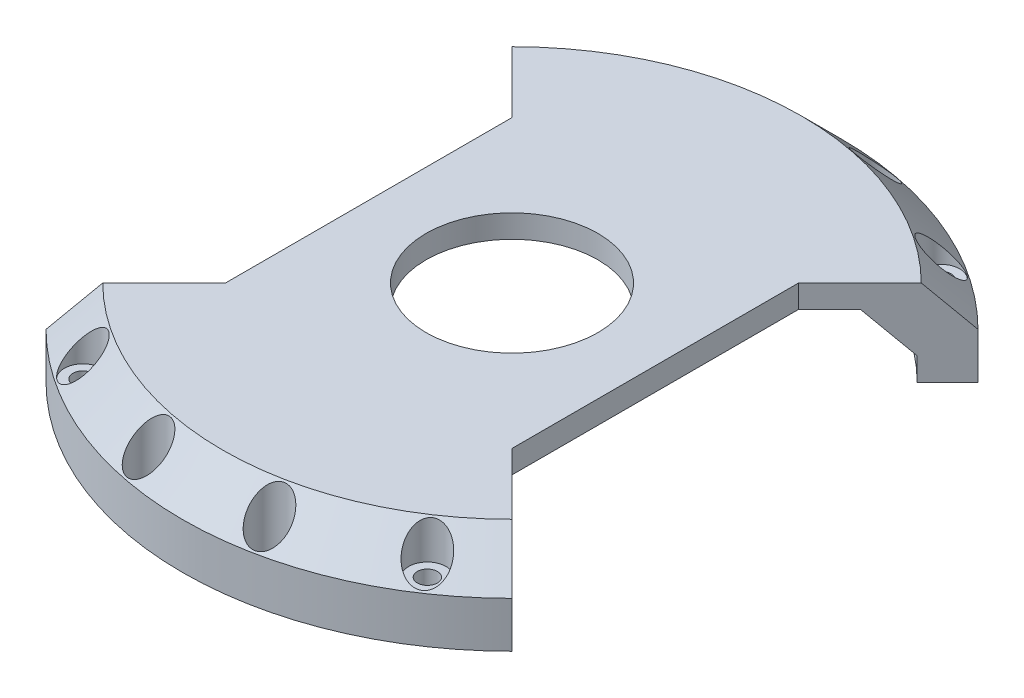
SolidWorks part; units mm, degrees
ref_plane "Front Plane" through (0, 0, 0) normal (0, 0, 1) x (1, 0, 0)
ref_plane "Top Plane" through (0, 0, 0) normal (0, 1, 0) x (1, 0, 0)
ref_plane "Right Plane" through (0, 0, 0) normal (1, 0, 0) x (0, 0, -1)
sketch "Sketch1" plane through (0, 0, 0) normal (0, 1, 0) x (1, 0, 0)
  circle A0 centre (0, 0) radius 57.5
  dimension "D1" = 115
extrude "Boss-Extrude1" add sketch "Sketch1" along normal blind 15
sketch "Sketch2" plane through (0, 0, 0) normal (0, -1, 0) x (1, 0, 0)
  circle A0 centre (0, 0) radius 50
  dimension "D1" = 100
extrude "Cut-Extrude1" cut sketch "Sketch2" against normal blind 11
sketch "Sketch3" plane through (0, 15, 0) normal (0, 1, 0) x (1, 0, 0)
  line L0 (0, 0) -> (0, 54) construction
  line L1 (0, 0) -> (-10.6273, 52.9439) construction
  circle A0 centre (0, 0) radius 54 construction
  circle A13 centre (0, 0) radius 15
  circle A14 centre (-10.6273, 52.9439) radius 1.75
  circle A15 centre (10.4424, 52.9807) radius 1.75
  circle A16 centre (29.9224, 44.9517) radius 1.75
  circle A17 centre (44.8469, 30.0791) radius 1.75
  circle A18 centre (52.9439, 10.6273) radius 1.75
  circle A19 centre (52.9807, -10.4424) radius 1.75
  circle A20 centre (44.9517, -29.9224) radius 1.75
  circle A21 centre (30.0791, -44.8469) radius 1.75
  circle A22 centre (10.6273, -52.9439) radius 1.75
  circle A23 centre (-10.4424, -52.9807) radius 1.75
  circle A24 centre (-29.9224, -44.9517) radius 1.75
  circle A25 centre (-44.8469, -30.0791) radius 1.75
  circle A26 centre (-52.9439, -10.6273) radius 1.75
  circle A27 centre (-52.9807, 10.4424) radius 1.75
  circle A28 centre (-44.9517, 29.9224) radius 1.75
  circle A29 centre (-30.0791, 44.8469) radius 1.75
  point P29 (0, 0)
  point P40 (0, 0)
  dimension "D1" = 108
  dimension "D2" = 11.35
  dimension "D4" = 30
  dimension "D3" = 3.5
extrude "Cut-Extrude2" cut sketch "Sketch3" against normal blind 15
sketch "Sketch4" plane through (0, 15, 0) normal (0, 1, 0) x (1, 0, 0)
  line L0 (25, 25) -> (40.6586, 40.6586)
  line L1 (-25, 25) -> (25, 25) construction
  line L2 (-25, 25) -> (-25, -25) construction
  line L3 (-25, -25) -> (25, -25) construction
  line L4 (25, 25) -> (25, -25)
  line L5 (-25, 25) -> (25, -25) construction
  line L6 (-25, -25) -> (25, 25) construction
  line L7 (25, -25) -> (40.6586, -40.6586)
  circle A0 centre (0, 0) radius 57.5 construction
  arc A1 (40.6586, -40.6586) -> (40.6586, 40.6586) centre (0, 0) ccw
  point P0 (0, 0)
  dimension "D1" = 50
extrude "Cut-Extrude3" cut sketch "Sketch4" against normal blind 15
mirror "Mirror1" about plane through (0, 0, 0) normal (1, 0, 0) of "Cut-Extrude3"
chamfer "Chamfer1" distance 7 angle 45 4 edges at (0, 15, -57.5) (0, 15, 57.5) (0, 11, 50) (0, 11, -50)
sketch "Sketch5" plane through (0, 15, 0) normal (0, 1, 0) x (1, 0, 0)
  line L0 (0, 0) -> (-10.6273, 52.9439) construction
  circle A0 centre (0, 0) radius 54 construction
  circle A1 centre (-10.6273, 52.9439) radius 3.25
  circle A2 centre (10.4424, 52.9807) radius 3.25
  circle A3 centre (29.9224, 44.9517) radius 3.25
  circle A4 centre (44.8469, 30.0791) radius 3.25
  circle A5 centre (52.9439, 10.6273) radius 3.25
  circle A6 centre (52.9807, -10.4424) radius 3.25
  circle A7 centre (44.9517, -29.9224) radius 3.25
  circle A8 centre (30.0791, -44.8469) radius 3.25
  circle A9 centre (10.6273, -52.9439) radius 3.25
  circle A10 centre (-10.4424, -52.9807) radius 3.25
  circle A11 centre (-29.9224, -44.9517) radius 3.25
  circle A12 centre (-44.8469, -30.0791) radius 3.25
  circle A13 centre (-52.9439, -10.6273) radius 3.25
  circle A14 centre (-52.9807, 10.4424) radius 3.25
  circle A15 centre (-44.9517, 29.9224) radius 3.25
  circle A16 centre (-30.0791, 44.8469) radius 3.25
  point P32 (0, 0)
  point P41 (0, 0)
  dimension "D1" = 6.5
extrude "Cut-Extrude4" cut sketch "Sketch5" against normal blind 7
sketch "Sketch6" plane through (0, 8, 0) normal (0, 1, 0) x (1, 0, 0)
  circle A0 centre (10.4424, 52.9807) radius 3.25
  circle A1 centre (-10.6273, 52.9439) radius 3.25
  circle A2 centre (-10.4424, -52.9807) radius 3.25
  circle A3 centre (10.6273, -52.9439) radius 3.25
extrude "Cut-Extrude5" cut sketch "Sketch6" against normal blind 44
